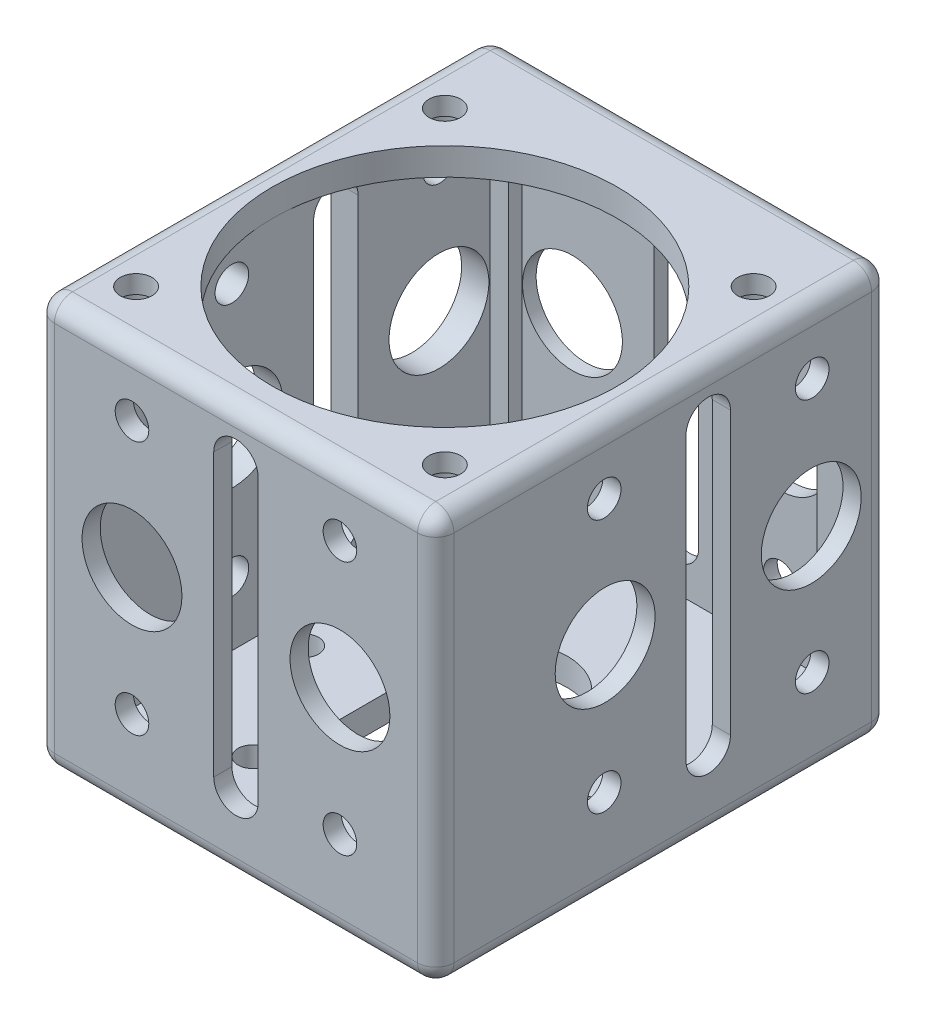
SolidWorks part; units mm, degrees
note: The reader was unsure of these and kept them because the rebuilt part matched: shared geometry of "草图1<6>", "草图24<5>".
ref_plane "前视基准面" through (0, 0, 0) normal (0, 0, 1) x (1, 0, 0)
ref_plane "上视基准面" through (0, 0, 0) normal (0, 1, 0) x (1, 0, 0)
ref_plane "右视基准面" through (0, 0, 0) normal (1, 0, 0) x (0, 0, -1)
other "Configuration Table"
sketch "草图1" plane through (0, 0, 0) normal (0, 1, 0) x (1, 0, 0)
  line L0 (0, 8.5) -> (0, -8.5)
  line L1 (-20, 20) -> (20, 20)
  line L2 (-20, 20) -> (-20, -20)
  line L3 (-20, -20) -> (20, -20)
  line L4 (20, 20) -> (20, -20)
  line L5 (-20, 20) -> (20, -20) construction
  line L6 (-20, -20) -> (20, 20) construction
  line L7 (0, 0) -> (-20, 0) construction
  line L8 (-18.5, -18.5) -> (18.5, -18.5)
  line L9 (18.5, 18.5) -> (18.5, -18.5)
  line L10 (-18.5, 18.5) -> (18.5, 18.5)
  line L11 (-18.5, 18.5) -> (-18.5, -18.5)
  circle A0 centre (0, 0) radius 12.6
  circle A1 centre (0, 8.5) radius 1.55
  circle A3 centre (0, 0) radius 4
  circle A4 centre (8.5, 0) radius 1.55
  circle A5 centre (0, -8.5) radius 1.55
  circle A6 centre (-8.5, 0) radius 1.55
  point P0 (0, 0)
  point P11 (0, 0)
  point P23 (0, 0)
  dimension "D4" = 25.2
  dimension "D6" = 3.1
  dimension "D7" = 8
  dimension "D8" = 4
  dimension "D1" = 40
  dimension "D2" = 40
  dimension "D3" = 20
  dimension "D5" = 17
  dimension "D10" = 1.5
  dimension "D9" = 1.5
extrude "凸台-拉伸2" add sketch "草图1" against normal blind 3 contours L2 L3 L4 L1 | A6 | A5 | A1 | A4
extrude "切除-拉伸1" cut sketch "草图1<6>" against normal blind 1.5 contours L0 A3 | L0 A3
sketch "草图1<6>" plane through (0, 0, 0) normal (0, 1, 0) x (1, 0, 0) same geometry as "草图1"
sketch "草图2" plane through (0, 0, 0) normal (0, 1, 0) x (1, 0, 0)
  line L0 (-20, -20) -> (20, -20) construction
  line L1 (20, 20) -> (20, -20) construction
  line L2 (-20, 20) -> (-20, -20) construction
  line L3 (-20, 20) -> (20, 20) construction
  line L4 (-20, -20) -> (20, -20)
  line L5 (20, 20) -> (20, -20)
  line L6 (-20, 20) -> (-20, -20)
  line L7 (-20, 20) -> (20, 20)
  line L8 (0, 0) -> (38.7801, 0) construction
  line L9 (-20, 20) -> (-17, 20)
  line L10 (-20, 20) -> (-20, 17)
  line L11 (-20, 17) -> (-17, 17)
  line L12 (-17, 20) -> (-17, 17)
  line L13 (0, 0) -> (0, 17.8693) construction
  line L14 (20, -17) -> (17, -17)
  line L15 (20, 20) -> (17, 20)
  line L16 (20, 20) -> (20, 17)
  line L17 (20, 17) -> (17, 17)
  line L18 (17, 20) -> (17, 17)
  line L19 (17, -20) -> (17, -17)
  line L20 (20, -20) -> (17, -20)
  line L21 (20, -20) -> (20, -17)
  line L22 (-20, -20) -> (-20, -17)
  line L23 (-20, -20) -> (-17, -20)
  line L24 (-17, -20) -> (-17, -17)
  line L25 (-20, -17) -> (-17, -17)
  circle A0 centre (0, -8.5) radius 1.55 construction
  circle A1 centre (8.5, 0) radius 1.55 construction
  circle A2 centre (0, 8.5) radius 1.55 construction
  circle A3 centre (0, 0) radius 4 construction
  circle A4 centre (-8.5, 0) radius 1.55 construction
  circle A5 centre (0, -8.5) radius 1.55
  circle A6 centre (8.5, 0) radius 1.55
  circle A7 centre (0, 8.5) radius 1.55
  circle A8 centre (0, 0) radius 4
  circle A9 centre (-8.5, 0) radius 1.55
  point P35 (18.5, -17)
  line M9 (20, 20) -> (-20, 20)
  line M10 (-20, 20) -> (-20, -20)
  line M11 (-20, -20) -> (20, -20)
  line M12 (20, -20) -> (20, 20)
  dimension "D1" = 3
  dimension "D2" = 3
  dimension "D3" = 34
  dimension "D4" = 34
  dimension "D5" = 34
  dimension "D6" = 34
extrude "凸台-拉伸7" add sketch "草图2" along normal blind 45 contours L12 L7 L11 M10 | L18 L17 M9 M12 | L19 L4 L14 M12 | L25 L24 M10 M11
sketch "草图5" plane through (-20, 0, 0) normal (-1, 0, 0) x (0, 0, 1)
  line L0 (20, -3) -> (20, 45) construction
  line L1 (-20, -3) -> (-20, 45) construction
  line L2 (20, -3) -> (20, 45)
  line L3 (-20, -3) -> (-20, 45)
  line L4 (-17, 0) -> (-17, 45)
  line L5 (-17, 45) -> (-17, 0) construction
  line L7 (-20, 45) -> (20, 45)
  line L8 (-20, 45) -> (-20, 42)
  line L9 (-20, 42) -> (20, 42)
  line L10 (20, 45) -> (20, 42)
extrude "凸台-拉伸8" add sketch "草图5" against normal blind 40 contours L8 L9 L10 L7
sketch "草图6" plane through (0, 45, 0) normal (0, 1, 0) x (1, 0, 0)
  line L0 (-20, -20) -> (0, -20)
  line L1 (0, -20) -> (0, 0)
  line L4 (20, -20) -> (20, 20)
  line L5 (20, 20) -> (-20, 20)
  line L6 (-20, 20) -> (-20, -20)
  line L7 (-20, -20) -> (20, -20)
  line L8 (20, -20) -> (20, 20)
  line L9 (20, 20) -> (-20, 20)
  line L10 (-20, 20) -> (-20, -20)
  line L11 (-20, -20) -> (20, -20)
  circle A0 centre (0, 0) radius 12.5
  dimension "D1" = 0
extrude "切除-拉伸2" cut sketch "草图6" against normal blind 4
sketch "草图7" plane through (0, -3, 0) normal (0, -1, 0) x (1, 0, 0)
  line L1 (-20, -20) -> (0, -20)
  line L2 (-20, -20) -> (-20, 0)
  line L3 (-20, 0) -> (0, 0)
  line L4 (-20, -20) -> (20, -20)
  line L5 (20, -20) -> (20, 20)
  line L6 (20, 20) -> (-20, 20)
  line L7 (-20, 20) -> (-20, -20)
  line L8 (-20, -20) -> (20, -20)
  line L9 (20, -20) -> (20, 20)
  line L10 (20, 20) -> (-20, 20)
  line L11 (-20, 20) -> (-20, -20)
  line L12 (0, -20) -> (0, 0)
  circle A0 centre (0, 0) radius 4
  dimension "D1" = 0
extrude "切除-拉伸3" cut sketch "草图7" against normal blind 4 contours L12 A0 L3 | L3 A0 L12
sketch "草图8" plane through (0, -3, 0) normal (0, -1, 0) x (1, 0, 0)
  line L0 (-20, 20) -> (0, 0) construction
  line L1 (0, 0) -> (20, 20) construction
  line L2 (-20, -20) -> (-20, 20) construction
  circle A0 centre (-12, 12) radius 5
  circle A1 centre (12, 12) radius 5
  circle A2 centre (12, -12) radius 5
  circle A3 centre (-12, -12) radius 5
  point P19 (0, 0)
  dimension "D1" = 8
  dimension "D2" = 4
extrude "切除-拉伸4" cut sketch "草图8" against normal blind 4
sketch "草图9" plane through (0, 45, 0) normal (0, 1, 0) x (1, 0, 0)
  line L0 (-20, 20) -> (0, 0) construction
  line L1 (0, 0) -> (20, 20) construction
  line L4 (20, -20) -> (20, 20)
  line L5 (20, 20) -> (-20, 20)
  line L6 (-20, 20) -> (-20, -20)
  line L7 (-20, -20) -> (20, -20)
  line L8 (20, -20) -> (20, 20)
  line L9 (20, 20) -> (-20, 20)
  line L10 (-20, 20) -> (-20, -20)
  line L11 (-20, -20) -> (20, -20)
  circle A0 centre (-12.7279, 12.7279) radius 2.5
  circle A1 centre (0, 0) radius 12.5 construction
  circle A2 centre (12.7279, 12.7279) radius 2.5
  circle A3 centre (12.7279, -12.7279) radius 2.5
  circle A4 centre (-12.7279, -12.7279) radius 2.5
  point P19 (0, 0)
  dimension "D2" = 18
  dimension "D3" = 4
  dimension "D1" = 0
extrude "切除-拉伸5" cut sketch "草图9" against normal blind 4 contours A0 | A4 | A2 | A3
sketch "草图10" plane through (0, 0, 0) normal (0, 1, 0) x (1, 0, 0)
  line L0 (20, -17) -> (17, -17) construction
  line L1 (20, 17) -> (18.5, 17)
  line L2 (20, 17) -> (20, -17)
  line L3 (20, -17) -> (18.5, -17)
  line L4 (18.5, 17) -> (18.5, -17)
  line L5 (17, -20) -> (-17, -20)
  line L6 (17, -20) -> (17, -18.5)
  line L7 (17, -18.5) -> (-17, -18.5)
  line L8 (-17, -20) -> (-17, -18.5)
  line L9 (-20, -17) -> (-20, 17)
  line L10 (-20, -17) -> (-18.5, -17)
  line L11 (-18.5, -17) -> (-18.5, 17)
  line L12 (-20, 17) -> (-18.5, 17)
  line L13 (-17, 20) -> (17, 20)
  line L14 (-17, 20) -> (-17, 18.5)
  line L15 (-17, 18.5) -> (17, 18.5)
  line L16 (17, 20) -> (17, 18.5)
  point P25 (0, 0)
  dimension "D1" = 4
extrude "凸台-拉伸10" add sketch "草图10" along normal blind 45
sketch "草图20" plane through (0, 0, 18.5) normal (0, 0, -1) x (-1, 0, 0)
  line L0 (0, 0) -> (0, 42)
  line L1 (-17, 0) -> (17, 0) construction
  line L2 (-20, -3) -> (-20, 45) construction
  line L3 (0, 0) -> (0, 3)
  line L4 (0, 3) -> (0, 5.5)
  line L5 (0, 21) -> (4.1437, 21)
  line L6 (-2.45, 36.5) -> (-2.45, 5.5)
  line L7 (2.45, 36.5) -> (2.45, 5.5)
  line L8 (-20, 45) -> (20, 45) construction
  line L9 (20, -3) -> (-20, -3) construction
  arc A1 (-2.45, 5.5) -> (2.45, 5.5) centre (0, 5.5) ccw
  arc A2 (-2.45, 36.5) -> (2.45, 36.5) centre (0, 36.5) cw
  point P10 (0, 45)
  point P13 (0, 38.95)
  point P20 (0, -3)
  point P21 (0, 3)
  dimension "D1" = 90
  dimension "D3" = 2.45
  dimension "D2" = 20
  dimension "D4" = 5.5
extrude "切除-拉伸12" cut sketch "草图20" against normal blind 4 and the other way through all contours L7 A1 L6 A2
sketch "草图24" plane through (20, 0, 0) normal (1, 0, 0) x (0, 0, -1)
  line L0 (0, -3) -> (0, 3)
  line L1 (0, 21) -> (-20, 21) construction
  line L2 (20, -3) -> (-20, -3) construction
  line L3 (0, 3) -> (0, 5.5)
  line L4 (0, -3) -> (0, 0)
  line L5 (0, 0) -> (0, 42)
  line L6 (0, 21) -> (5.4047, 21)
  line L7 (-2.45, 36.5) -> (-2.45, 5.5)
  line L8 (2.45, 5.5) -> (2.45, 36.5)
  line L9 (-20, 45) -> (20, 45) construction
  line L12 (-11.35, -3) -> (-11.35, 45) construction
  line L13 (-11.35, 21) -> (-11.35, 49) construction
  line L16 (20, -3) -> (20, 45)
  line L17 (20, 45) -> (-20, 45)
  line L18 (-20, 45) -> (-20, -3)
  line L19 (-20, -3) -> (20, -3)
  line L20 (20, -3) -> (20, 45)
  line L21 (20, 45) -> (-20, 45)
  line L22 (-20, 45) -> (-20, -3)
  line L23 (-20, -3) -> (20, -3)
  arc A0 (-2.45, 5.5) -> (2.45, 5.5) centre (0, 5.5) ccw
  arc A1 (-2.45, 36.5) -> (2.45, 36.5) centre (0, 36.5) cw
  circle A2 centre (-11.45, 35) radius 1.85
  circle A3 centre (-11.45, 7) radius 1.85
  circle A4 centre (11.45, 7) radius 1.85
  circle A5 centre (11.45, 35) radius 1.85
  circle A6 centre (-11.35, 21) radius 5.5
  circle A7 centre (11.35, 21) radius 5.5
  point P7 (0, 38.95)
  point P13 (0, 45)
  point P18 (0, 3.05)
  point P37 (-11.45, 35)
  dimension "D1" = 3
  dimension "D3" = 9
  dimension "D4" = 3.7
  dimension "D6" = 10
  dimension "D7" = 8.65
  dimension "D8" = 2.45
  dimension "D2" = 8.5
  dimension "D5" = 0
extrude "切除-拉伸13" cut sketch "草图24" along normal blind 4 and the other way through all contours L7 A0 L8 A1
extrude "切除-拉伸15" cut sketch "草图24<5>" along normal blind 10 and the other way through all contours A2 | A5 | A6 | A7 | A3 | A4
sketch "草图24<5>" plane through (20, 0, 0) normal (1, 0, 0) x (0, 0, -1) same geometry as "草图24"
sketch "草图25" plane through (0, 0, -20) normal (0, 0, -1) x (-1, 0, 0)
  line L0 (-11.45, -3) -> (-11.45, 45) construction
  line L1 (-2.45, 36.5) -> (-2.45, 5.5) construction
  line L2 (-11.45, 21) -> (-31.2071, 21) construction
  line L3 (-11.45, 45) -> (-11.45, 35) construction
  line L4 (20, -3) -> (20, 45)
  line L5 (20, 45) -> (-20, 45)
  line L6 (-20, 45) -> (-20, -3)
  line L7 (-20, -3) -> (20, -3)
  line L8 (20, -3) -> (20, 45)
  line L9 (20, 45) -> (-20, 45)
  line L10 (-20, 45) -> (-20, -3)
  line L11 (-20, -3) -> (20, -3)
  line L12 (0, 0) -> (0, 45) construction
  line L13 (-2.45, 36.5) -> (-2.45, 5.5)
  circle A0 centre (-11.45, 21) radius 5.5
  circle A1 centre (-11.45, 35) radius 1.85
  circle A2 centre (11.45, 35) radius 1.85
  circle A3 centre (11.45, 7) radius 1.85
  circle A4 centre (-11.45, 7) radius 1.85
  circle A5 centre (11.45, 21) radius 5.5
  dimension "D3" = 10
  dimension "D4" = 11
  dimension "D2" = 9
  dimension "D1" = 0
extrude "切除-拉伸16" cut sketch "草图25" along normal blind 10 and the other way through all contours A0 | A5 | A1 | A4 | A3 | A2
sketch "草图27" plane through (0, -3, 0) normal (0, -1, 0) x (1, 0, 0)
  circle A0 centre (-12, 12) radius 5
  circle A1 centre (12, 12) radius 5
  circle A2 centre (12, -12) radius 5
  circle A3 centre (-12, -12) radius 5
  circle A4 centre (0, -8.5) radius 1.55
  circle A5 centre (8.5, 0) radius 1.55
  circle A6 centre (0, 8.5) radius 1.55
  circle A7 centre (-8.5, 0) radius 1.55
extrude "凸台-拉伸11" add sketch "草图27" against normal blind 3
sketch "草图28" plane through (0, -3, 0) normal (0, -1, 0) x (1, 0, 0)
  line L0 (0, 0) -> (0, 7)
  circle A1 centre (0, 7) radius 15.5
  dimension "D1" = 7
  dimension "D2" = 31
sketch "草图31" plane through (0, 0, 18.5) normal (0, 0, -1) x (-1, 0, 0)
  line L0 (-20, 45) -> (20, 45) construction
  line L1 (-20, 45) -> (20, 45)
  line L2 (-20, 45) -> (-20, -3)
  line L3 (-20, -3) -> (20, -3)
  line L4 (20, 45) -> (20, -3)
  line L5 (-20, -3) -> (-20, 45) construction
extrude "凸台-拉伸12" add sketch "草图31" against normal blind 20
sketch "草图32" plane through (0, 45, 0) normal (0, 1, 0) x (1, 0, 0)
  line L1 (-20, 20) -> (20, 20)
  line L2 (-20, 20) -> (-20, -38.5)
  line L3 (-20, -38.5) -> (20, -38.5)
  line L4 (20, 20) -> (20, -38.5)
extrude "凸台-拉伸13" add sketch "草图32" against normal blind 3
sketch "草图33" plane through (0, -3, 0) normal (0, -1, 0) x (1, 0, 0)
  line L0 (0, 0) -> (0, 14)
  line L1 (-6.5, 14) -> (-6.5, 0)
  line L2 (6.5, 14) -> (6.5, 0)
  line L3 (-6.5, 0) -> (6.5, 0)
  line L4 (-6.5, 14) -> (6.5, 14)
  circle A0 centre (0, 7) radius 15.5
  circle A1 centre (-15.5, 7) radius 1.6
  circle A2 centre (-7.75, 20.4234) radius 1.6
  circle A3 centre (7.75, 20.4234) radius 1.6
  circle A4 centre (15.5, 7) radius 1.6
  circle A5 centre (7.75, -6.4234) radius 1.6
  circle A6 centre (-7.75, -6.4234) radius 1.6
  circle A7 centre (0, 0) radius 6.5
  circle A8 centre (0, 14) radius 6.5
  circle M12 centre (0, 0) radius 4
  dimension "D1" = 3.2
  dimension "D3" = 13
  dimension "D5" = 13
  dimension "D4" = 14
  dimension "D2" = 6
extrude "切除-拉伸17" cut sketch "草图33" against normal blind 3 contours A0 A2 | A0 A2 | A8 L0 A7 L2 | A8 L1 A7 L0 | L4 A8 L0 | L0 A8 L4 | L4 A8 | L3 A7 M12 | L0 A7 L3 M12 | L3 A7 L0 M12 | A1 | A6 | A5 | A4 | A3
sketch "草图34" plane through (0, 42, 0) normal (0, -1, 0) x (1, 0, 0)
  circle A0 centre (0, 7) radius 19
  dimension "D1" = 38
extrude "切除-拉伸18" cut sketch "草图34" against normal blind 3
sketch "草图35" plane through (0, 42, 0) normal (0, 1, 0) x (1, 0, 0)
  circle A0 centre (0, -7) radius 19
extrude "切除-拉伸20" cut sketch "草图35" against normal blind 42
sketch "草图36" plane through (0, 0, 38.5) normal (0, 0, 1) x (1, 0, 0)
  line L1 (-20, 45) -> (20, 45)
  line L2 (-20, 45) -> (-20, -3)
  line L3 (-20, -3) -> (20, -3)
  line L4 (20, 45) -> (20, -3)
extrude "切除-拉伸21" cut sketch "草图36" against normal blind 10.5
ref_plane "基准面2" through (0, 22, 0) normal (0, 1, 0) x (1, 0, 0)
sketch "草图39" plane through (0, 45, 0) normal (0, 1, 0) x (1, 0, 0)
  line L0 (-17, 10) -> (17, 10)
  line L1 (-20, -27) -> (20, -27)
  line L2 (-20, -27) -> (-20, 13)
  line L3 (-20, 13) -> (20, 13)
  line L4 (20, -27) -> (20, 13)
  line L5 (-20, -27) -> (20, 13) construction
  line L6 (-20, 13) -> (20, -27) construction
  line L7 (17, -24) -> (17, 10)
  line L8 (-17, -24) -> (17, -24)
  line L9 (-17, -24) -> (-17, 10)
  circle A0 centre (-17, 10) radius 1.5
  circle A1 centre (17, 10) radius 1.5
  circle A2 centre (-17, -24) radius 1.5
  circle A3 centre (17, -24) radius 1.5
  point P0 (0, -7)
  dimension "D4" = 3
  dimension "D5" = 3
  dimension "D6" = 3
  dimension "D7" = 3
  dimension "D1" = 40
  dimension "D2" = 40
  dimension "D3" = 3
extrude "切除-拉伸22" cut sketch "草图39" against normal blind 3 contours A0 | A2 | A3 | A1
sketch "草图44" plane through (-20, 0, 0) normal (-1, 0, 0) x (0, 0, 1)
  line L1 (-20, 45) -> (28, 45)
  line L2 (-20, 45) -> (-20, -3)
  line L3 (-20, -3) -> (28, -3)
  line L4 (28, 45) -> (28, -3)
extrude "凸台-拉伸17" add sketch "草图44" along normal blind 2
sketch "草图45" plane through (20, 0, 0) normal (1, 0, 0) x (0, 0, -1)
  line L1 (-28, 45) -> (20, 45)
  line L2 (-28, 45) -> (-28, -3)
  line L3 (-28, -3) -> (20, -3)
  line L4 (20, 45) -> (20, -3)
extrude "凸台-拉伸18" add sketch "草图45" along normal blind 2
sketch "草图46" plane through (20, 0, 0) normal (-1, 0, 0) x (0, 0, 1)
  line L1 (-20, -3) -> (-17, -3)
  line L2 (-20, -3) -> (-20, 0)
  line L3 (-20, 0) -> (-17, 0)
  line L4 (-17, -3) -> (-17, 0)
  line L5 (28, 45) -> (25, 45)
  line L6 (28, 45) -> (28, 42)
  line L7 (28, 42) -> (25, 42)
  line L8 (25, 45) -> (25, 42)
  line L9 (-17, 0) -> (25, 0)
  line L10 (-17, 0) -> (-17, 42)
  line L11 (-17, 42) -> (25, 42)
  line L12 (25, 0) -> (25, 42)
  dimension "D1" = 3
  dimension "D2" = 3
  dimension "D3" = 3
  dimension "D4" = 3
extrude "切除-拉伸23" cut sketch "草图46" along normal blind 2 contours L6 L1 L2 L5 | L9 L12 L11 L10 L1 L6 L5 L2
sketch "草图47" plane through (-20, 0, 0) normal (1, 0, 0) x (0, 0, -1)
  line L0 (-11.35, -3) -> (-11.35, 45) construction
  line L1 (-2.45, 36.5) -> (-2.45, 5.5)
  line L2 (2.45, 36.5) -> (2.45, 5.5)
  circle A0 centre (-11.35, 21) radius 5.5
  circle A1 centre (-11.45, 35) radius 1.85
  circle A2 centre (11.45, 35) radius 1.85
  circle A3 centre (11.45, 7) radius 1.85
  circle A4 centre (-11.45, 7) radius 1.85
  circle A5 centre (11.35, 21) radius 5.5
  circle A6 centre (0, 36.5) radius 2.45
  circle A7 centre (0, 5.5) radius 2.45
sketch "草图51" plane through (-20, 0, 0) normal (1, 0, 0) x (0, 0, -1)
  line L1 (-25, 42) -> (17, 42)
  line L2 (-25, 42) -> (-25, 0)
  line L3 (-25, 0) -> (17, 0)
  line L4 (17, 42) -> (17, 0)
extrude "切除-拉伸28" cut sketch "草图51" along normal blind 2 and the other way through all
sketch "草图53" plane through (-22, 0, 0) normal (-1, 0, 0) x (0, 0, 1)
  line L1 (-17, 42) -> (25, 42)
  line L2 (-17, 42) -> (-17, 0)
  line L3 (-17, 0) -> (25, 0)
  line L4 (25, 42) -> (25, 0)
extrude "凸台-拉伸19" add sketch "草图53" against normal blind 3
sketch "草图56" plane through (20, 0, 0) normal (-1, 0, 0) x (0, 0, 1)
  line L0 (-2.45, 36.5) -> (-2.45, 5.5)
  line L1 (2.45, 36.5) -> (2.45, 5.5)
  circle A0 centre (-11.45, 35) radius 1.85
  circle A1 centre (-11.35, 21) radius 5.5
  circle A2 centre (11.35, 21) radius 5.5
  circle A3 centre (11.45, 35) radius 1.85
  circle A4 centre (11.45, 7) radius 1.85
  circle A5 centre (-11.45, 7) radius 1.85
  circle A6 centre (0, 5.5) radius 2.45
  circle A7 centre (0, 36.5) radius 2.45
extrude "切除-拉伸30" cut sketch "草图56" against normal through all both and the other way through all contours A1 | A0 | A5 | A6 | A7 L0 A6 L1 | A7 | A2 | A4 | A3
sketch "草图57" plane through (0, 45, 0) normal (0, 1, 0) x (1, 0, 0)
  circle A0 centre (-17, -24) radius 1.5
sketch "草图60" plane through (0, 0, 0) normal (0, 1, 0) x (1, 0, 0)
  line L0 (22, -28) -> (-22, -28) construction
  line L1 (-19, -25) -> (19, -25)
  line L2 (-19, -25) -> (-19, 11)
  line L3 (-19, 11) -> (19, 11)
  line L4 (19, -25) -> (19, 11)
  line L5 (-19, -25) -> (19, 11) construction
  line L6 (-19, 11) -> (19, -25) construction
  line L7 (-22, -28) -> (-22, 20) construction
  point P0 (0, -7)
  dimension "D1" = 3
  dimension "D2" = 3
extrude "切除-拉伸32" cut sketch "草图60" along normal blind 42
sketch "草图61" plane through (0, 0, 28) normal (0, 0, 1) x (1, 0, 0)
  line L1 (-22, 45) -> (22, 45)
  line L2 (-22, 45) -> (-22, -3)
  line L3 (-22, -3) -> (22, -3)
  line L4 (22, 45) -> (22, -3)
extrude "凸台-拉伸20" add sketch "草图61" along normal blind 2
ref_plane "基准面4" through (0, 0, 28) normal (0, 0, 1) x (1, 0, 0)
sketch "草图62" plane through (0, 0, 28) normal (0, 0, 1) x (1, 0, 0)
  line L1 (-22, -3) -> (-19, -3)
  line L2 (-22, -3) -> (-22, 0)
  line L3 (-22, 0) -> (-19, 0)
  line L4 (-19, -3) -> (-19, 0)
  line L5 (22, 45) -> (19, 45)
  line L6 (22, 45) -> (22, 42)
  line L7 (22, 42) -> (19, 42)
  line L8 (19, 45) -> (19, 42)
  line L9 (-19, 0) -> (19, 0)
  line L10 (-19, 0) -> (-19, 42)
  line L11 (-19, 42) -> (19, 42)
  line L12 (19, 0) -> (19, 42)
  dimension "D1" = 3
  dimension "D2" = 3
  dimension "D3" = 3
  dimension "D4" = 3
extrude "切除-拉伸33" cut sketch "草图62" against normal blind 20 contours L9 L12 L11 L10
sketch "草图63" plane through (0, 0, 30) normal (0, 0, 1) x (1, 0, 0)
  circle A0 centre (-11.45, 35) radius 1.85
  circle A1 centre (-11.45, 21) radius 5.5
  circle A2 centre (-11.45, 7) radius 1.85
  circle A3 centre (11.45, 7) radius 1.85
  circle A4 centre (11.45, 21) radius 5.5
  circle A5 centre (11.45, 35) radius 1.85
extrude "切除-拉伸34" cut sketch "草图63" against normal blind 3
sketch "草图64" plane through (0, 0, 30) normal (0, 0, 1) x (1, 0, 0)
  line L0 (-2.45, 36.5) -> (-2.45, 5.5)
  line L1 (2.45, 36.5) -> (2.45, 5.5)
  circle A0 centre (0, 36.5) radius 2.45
  circle A1 centre (0, 5.5) radius 2.45
extrude "切除-拉伸35" cut sketch "草图64" against normal blind 3 contours A1 L1 A0 L0 | A0 | A1
sketch "草图66" plane through (0, 45, 0) normal (0, 1, 0) x (1, 0, 0)
  line L1 (-22, 20) -> (-19, 20)
  line L2 (-22, 20) -> (-22, 17)
  line L3 (-22, 17) -> (-19, 17)
  line L4 (-19, 20) -> (-19, 17)
  line L9 (22, 20) -> (22, -30) construction
  line L10 (22, -30) -> (19, -30)
  line L11 (22, -30) -> (22, -27)
  line L12 (22, -27) -> (19, -27)
  line L13 (19, -30) -> (19, -27)
  line L14 (22, -30) -> (-22, -30) construction
  line L16 (-19, 17) -> (19, 17)
  line L17 (-19, 17) -> (-19, -27)
  line L18 (-19, -27) -> (19, -27)
  line L19 (19, 17) -> (19, -27)
  dimension "D1" = 3
  dimension "D2" = 3
  dimension "D3" = 3
  dimension "D4" = 3
sketch "草图67" plane through (0, 45, 0) normal (0, 1, 0) x (1, 0, 0)
  line L1 (-22, 20) -> (22, 20)
  line L2 (-22, 20) -> (-22, -30)
  line L3 (-22, -30) -> (22, -30)
  line L4 (22, 20) -> (22, -30)
  circle A0 centre (-17, 10) radius 1.5
  circle A1 centre (17, 10) radius 1.5
  circle A2 centre (17, -24) radius 1.5
  circle A3 centre (-17, -24) radius 1.5
  circle A4 centre (0, -7) radius 19
extrude "凸台-拉伸21" add sketch "草图67" against normal blind 6
sketch "草图68" plane through (0, 45, 0) normal (0, 1, 0) x (1, 0, 0)
  line L1 (-22, 20) -> (22, 20)
  line L2 (-22, 20) -> (-22, -30)
  line L3 (-22, -30) -> (22, -30)
  line L4 (22, 20) -> (22, -30)
extrude "切除-拉伸36" cut sketch "草图68" against normal blind 3
sketch "草图69" plane through (0, 39, 0) normal (0, -1, 0) x (1, 0, 0)
  line L0 (24.2, 28) -> (-24.2, 28) construction
  line L1 (-22, 30) -> (-20.5328, 30)
  line L2 (-22, 30) -> (-22, 28)
  line L3 (-22, 28) -> (-20.5328, 28)
  line L4 (-20.5328, 30) -> (-20.5328, 28)
sketch "草图71" plane through (0, 39, 0) normal (0, -1, 0) x (1, 0, 0)
  circle A0 centre (-17, 24) radius 2.5
  circle A2 centre (17, 24) radius 2.5
  circle A3 centre (17, -10) radius 2.5
  circle A4 centre (-17, -10) radius 2.5
  dimension "D1" = 5
  dimension "D2" = 4
extrude "切除-拉伸41" cut sketch "草图71" against normal blind 1
sketch "草图72" plane through (0, 42, 0) normal (0, 1, 0) x (1, 0, 0)
  circle A0 centre (-17, 10) radius 1.75
  circle A1 centre (17, 10) radius 1.75
  circle A2 centre (17, -24) radius 1.75
  circle A3 centre (-17, -24) radius 1.75
  dimension "D1" = 3.5
  dimension "D2" = 3.5
  dimension "D3" = 3.5
  dimension "D4" = 3.5
extrude "切除-拉伸42" cut sketch "草图72" against normal blind 3
sketch "草图73" plane through (0, 39, 0) normal (0, 1, 0) x (1, 0, 0)
  circle A0 centre (-17, -24) radius 2.5
  circle A1 centre (-17, 10) radius 2.5
  dimension "D1" = 5
  dimension "D2" = 5
extrude "切除-拉伸43" cut sketch "草图73" against normal blind 2
fillet "圆角6" radius 2 4 edges at (-22, 42, 5) (0, 42, -20) (22, 42, 5) (0, 42, 30)
fillet "圆角7" radius 2 5 edges at (0, -3, 30) (22, 18.5, 30) (-22, 18.5, 30) (-21.4142, 41.4142, 29.4142) (21.4142, 41.4142, 29.4142)
fillet "圆角8" radius 2 4 edges at (22, 18.5, -20) (21.4142, 41.4142, -19.4142) (22, -3, 4) (21.4142, -2.4142, 29.4142)
fillet "圆角9" radius 2 4 edges at (-22, -3, 4) (-21.4142, -2.4142, 29.4142) (21.4142, -2.4142, -19.4142) (-1, -3, -20)
fillet "圆角10" radius 2 3 edges at (-22, 19.5, -20) (-21.4142, 41.4142, -19.4142) (-21.4142, -2.4142, -19.4142)
